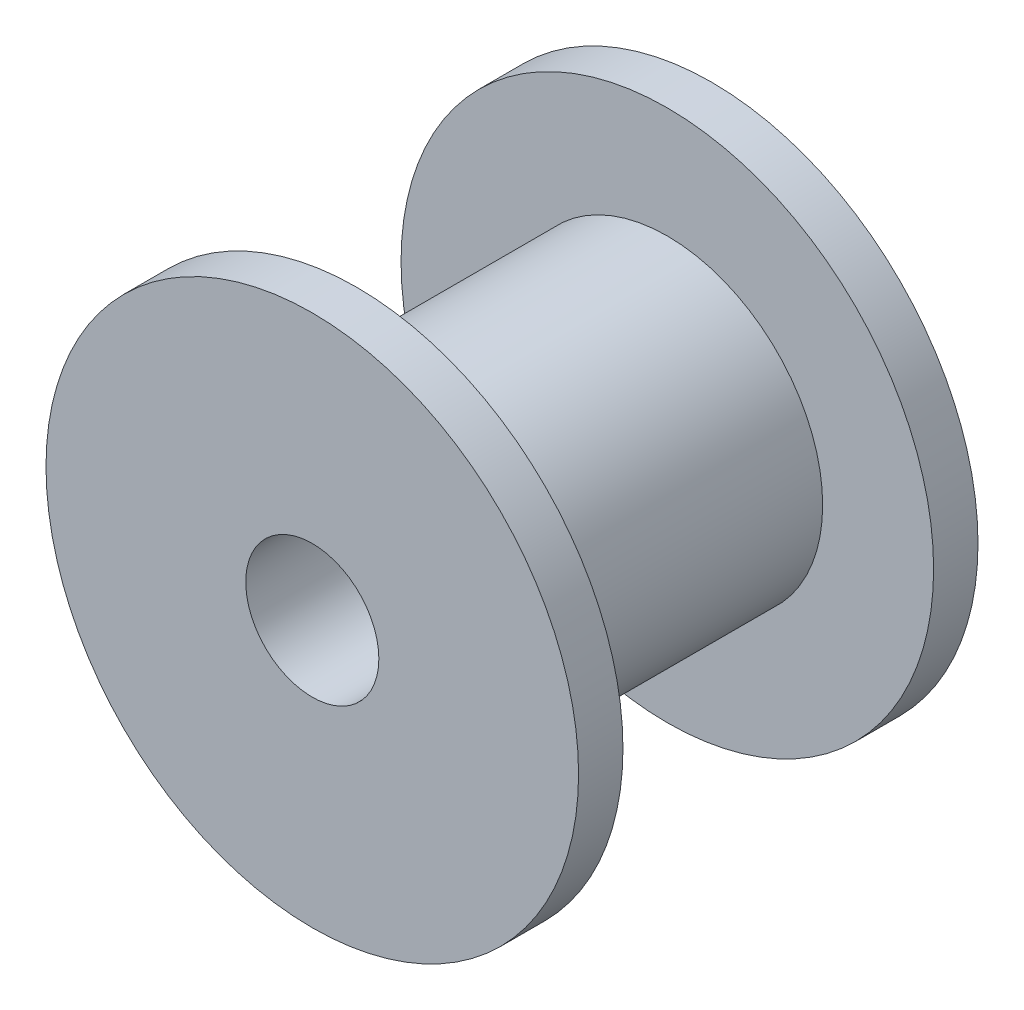
SolidWorks part; units mm, degrees
ref_plane "Front Plane" through (0, 0, 0) normal (0, 0, 1) x (1, 0, 0)
ref_plane "Top Plane" through (0, 0, 0) normal (0, 1, 0) x (1, 0, 0)
ref_plane "Right Plane" through (0, 0, 0) normal (1, 0, 0) x (0, 0, -1)
sketch "Sketch2" plane through (0, 0, 0) normal (0, 0, 1) x (1, 0, 0)
  circle A0 centre (0, 0) radius 6
  circle A1 centre (0, 0) radius 3.5
  circle A2 centre (0, 0) radius 1.5
extrude "Boss-Extrude1" add sketch "Sketch2" along normal blind 9 contours A2 | A0 region at (0, 0, 0)
extrude "Cut-Extrude-Thin1" cut sketch "Sketch2<3>" along normal blind 7 from offset 1 thin contours A1 thin type one direction wall 10
sketch "Sketch2<3>" plane through (0, 0, 0) normal (0, 0, 1) x (1, 0, 0) same geometry as "Sketch2"
